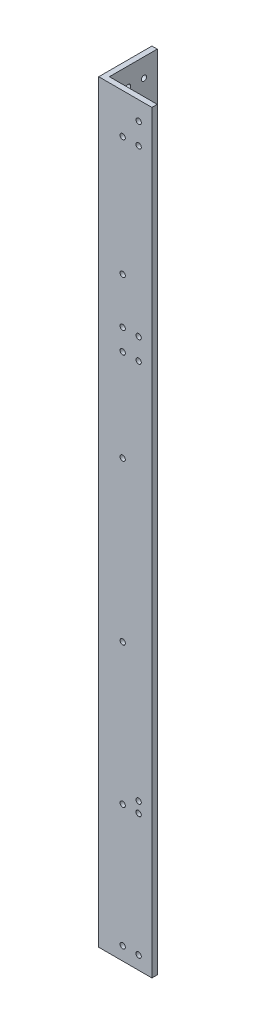
SolidWorks part; units mm, degrees
ref_plane "Front Plane" through (0, 0, 0) normal (0, 0, 1) x (1, 0, 0)
ref_plane "Top Plane" through (0, 0, 0) normal (0, 1, 0) x (1, 0, 0)
ref_plane "Right Plane" through (0, 0, 0) normal (1, 0, 0) x (0, 0, -1)
sketch "Sketch2" plane through (0, 0, 0) normal (0, 1, 0) x (1, 0, 0)
  line L0 (0, 31.75) -> (3.175, 31.75)
  line L1 (3.175, 31.75) -> (3.175, 3.175)
  line L2 (3.175, 3.175) -> (31.75, 3.175)
  line L3 (31.75, 3.175) -> (31.75, 0)
  line L4 (31.75, 0) -> (0, 0)
  line L5 (0, 0) -> (0, 31.75)
  point P9 (1.5875, 31.75)
  point P10 (31.75, 1.5875)
  dimension "D4" = 3.175
  dimension "D1" = 31.75
  dimension "D2" = 31.75
  dimension "D3" = 3.175
extrude "Boss-Extrude1" add sketch "Sketch2" along normal blind 450
sketch "RightSideHoles-Sketch3" plane through (0, 0, 0) normal (0, 0, 1) x (1, 0, 0)
  line L0 (0, 0) -> (31.75, 0) construction
  line L1 (0, 450) -> (31.75, 450) construction
  line L3 (0, 450) -> (0, 0) construction
  circle A0 centre (14.2875, 81.1125) radius 1.5875
  circle A1 centre (23.8125, 81.1125) radius 1.5875
  circle A3 centre (23.8125, 87.4625) radius 1.5875
  circle A5 centre (14.2875, 426.1875) radius 1.5875
  circle A6 centre (23.8125, 438.8875) radius 1.5875
  circle A7 centre (23.8125, 426.1875) radius 1.5875
  circle A8 centre (14.2875, 327.6026) radius 1.5875
  circle A9 centre (23.8125, 327.6026) radius 1.5875
  circle A10 centre (14.2875, 314.9026) radius 1.5875
  circle A11 centre (23.8125, 314.9026) radius 1.5875
  circle A12 centre (14.2875, 7.9375) radius 1.5875
  circle A13 centre (23.8125, 7.9375) radius 1.5875
  circle A14 centre (14.2875, 165) radius 1.5875
  circle A15 centre (14.2875, 260) radius 1.5875
  circle A16 centre (14.2875, 355) radius 1.5875
  dimension "D4" = 3.175
  dimension "D1" = 81.1125
  dimension "D2" = 14.2875
  dimension "D12" = 7.9375
  dimension "D7" = 12.7
  dimension "D3" = 9.525
  dimension "D10" = 327.6026
  dimension "D11" = 165
  dimension "D13" = 95
  dimension "D14" = 95
  dimension "D5" = 6.35
  dimension "D6" = 12.7
  dimension "D8" = 11.1125
sketch "FrontSideHoles-Sketch4" plane through (0, 0, 0) normal (-1, 0, 0) x (0, 0, 1)
  line L0 (-31.75, 450) -> (0, 450) construction
  line L1 (0, 450) -> (0, 0) construction
  line L3 (-31.75, 0) -> (0, 0) construction
  circle A0 centre (-23.8125, 81.1125) radius 1.5875
  circle A2 centre (-23.8125, 87.4625) radius 1.5875
  circle A3 centre (-14.2875, 87.4625) radius 1.5875
  circle A4 centre (-23.8125, 438.8875) radius 1.5875
  circle A5 centre (-14.2875, 438.8875) radius 1.5875
  circle A6 centre (-23.8125, 426.1875) radius 1.5875
  circle A8 centre (-14.2875, 333.1776) radius 2
  circle A9 centre (-14.2875, 314.6526) radius 2
  circle A10 centre (-14.2875, 165) radius 1.5875
  circle A11 centre (-14.2875, 260) radius 1.5875
  circle A12 centre (-14.2875, 355) radius 1.5875
  circle A13 centre (-23.8125, 7.9375) radius 1.5875
  circle A14 centre (-14.2875, 7.9375) radius 1.5875
  dimension "D4" = 3.175
  dimension "D7" = 12.7
  dimension "D13" = 95
  dimension "D14" = 95
  dimension "D5" = 6.35
  dimension "D16" = 4
  dimension "D6" = 11.1125
  dimension "D9" = 18.525
  dimension "D10" = 14.2875
  dimension "D8" = 314.6526
  dimension "D12" = 165
  dimension "D15" = 7.9375
  dimension "D2" = 14.2875
  dimension "D11" = 9.525
  dimension "D3" = 81.1125
extrude "RightSideHoles-Cut-Extrude1" cut sketch "RightSideHoles-Sketch3" against normal blind 3.175
extrude "FrontSideHoles-Cut-Extrude2" cut sketch "FrontSideHoles-Sketch4" against normal blind 3.175
equation "\"RailThickness\"= .125in'Spec"
equation "\"VSWidth\"= 1.25in'Spec"
equation "\"VSHeight\"= 1.25in'Spec"
equation "\"VSLength\"= 450mm"
equation "\"HoleOffsetFromEdge\"= \"RailThickness\" * 2.5"
equation "\"HoleOffsetFromSide\"= \"RailThickness\" * 3.5"
equation "\"LegHeight\"= 70mm'Space needed for PSU/Stepper/Electronics"
equation "\"VSBottomSideRailHoleY1FromBottomOfLowerRail\"= \"V1 BottomOfLowerRail\" + \"HoleOffsetFromSide\"'Equals 70.1125"
equation "\"VSSideRailHoleX1FromSide\"= \"HoleOffsetFromSide\" + \"RailThickness\""
equation "\"FasteningHoleDiameter\"= .125in"
equation "\"VSBottomSideRailHoleY2FromY1\"= \"LowerRailHeight\" - \"HoleOffsetFromSide\" - \"HoleOffsetFromEdge\"'Equals 6.35"
equation "\"VSTopSideRailHoleY1FromEdge\"= \"HoleOffsetFromEdge\" + \"RailThickness\""
equation "\"D4@RightSideHoles-Sketch3\" = \"FasteningHoleDiameter\""
equation "\"D1@RightSideHoles-Sketch3\" = \"VSBottomSideRailHoleY1FromBottomOfLowerRail\""
equation "\"D2@RightSideHoles-Sketch3\" = \"VSSideRailHoleX1FromSide\""
equation "\"D1@Boss-Extrude1\"=\"VSLength\""
equation "\"D4@FrontSideHoles-Sketch4\" = \"FasteningHoleDiameter\""
equation "\"D6@FrontSideHoles-Sketch4\" = \"VSTopSideRailHoleY1FromEdge\""
equation "\"VSMidSideRailHoleY1FromV8TopOfMidSideRail\"= \"V8 ToTopOfMidSideRail\" - \"HoleOffsetFromEdge\"'Equals 308.2875"
equation "\"LowerRailHeight\"= 1.00in"
equation "\"D2@Sketch2\"=\"VSWidth\""
equation "\"D1@Sketch2\"=\"VSHeight\""
equation "\"TopRailHeight\"= 1.25in"
equation "\"MidSideRailHeight\"= 1.25in"
equation "\"D12@RightSideHoles-Sketch3\"=\"HoleOffsetFromEdge\""
equation "\"VSMidSideRailHoleY2FromY1\"= \"MidSideRailHeight\" - \"HoleOffsetFromSide\" - \"HoleOffsetFromEdge\"'Equals 12.7"
equation "\"D7@RightSideHoles-Sketch3\"=\"VSMidSideRailHoleY2FromY1\""
equation "\"VSTopSideRailHoleY2FromY1\"= \"TopRailHeight\" - \"VSTopSideRailHoleY1FromEdge\" - \"HoleOffsetFromEdge\"'Equals 12.7"
equation "\"D7@FrontSideHoles-Sketch4\"=\"VSTopSideRailHoleY2FromY1\""
equation "\"VSSideRailHoleX2FromX1\"= \"VSWidth\" - \"VSSideRailHoleX1FromSide\" - \"HoleOffsetFromEdge\""
equation "\"D3@RightSideHoles-Sketch3\"=\"VSSideRailHoleX2FromX1\""
equation "\"1mmSpacer\"= 1mm"
equation "\"20TGT2PulleyWidth\"= 8.7mm'The STL of the Pulley in the diagram is a bit larger"
equation "\"BeltTensionerUpperLowerWallThickness\"= 7mm"
equation "\"BeltTensionerInnerHeight\"= \"20TGT2PulleyWidth\" * 2 + \"1mmSpacer\" * 3"
equation "\"BeltTensionerHeight\"= \"BeltTensionerInnerHeight\" + \"BeltTensionerUpperLowerWallThickness\" * 2"
equation "\"D9@FrontSideHoles-Sketch4\"=\"VSBeltTensionerHoleY2FromY1\""
equation "\"VSBeltTensionerHoleY1FromBottom\"= \"V9 FromBottomGantryPulleyToBottomOfBeltTensioner\" + \"HoleOffsetFromEdge\""
equation "\"VSBeltTensionerHoleY2FromY1\"= \"BeltTensionerHeight\" - \"HoleOffsetFromEdge\" * 2"
equation "\"V1 BottomOfLowerRail\"= \"LegHeight\""
equation "\"StepperShaftLength\"= 24mm'Pulley will be attached to the end"
equation "\"ZAxisLeadScrewLength\"= 200mm"
equation "\"LM8UUHeight\"= 24mm'Spec"
equation "\"V2 ToBedAtTopOfZAxis\" = \"V1 BottomOfLowerRail\" - \"LowerEnclosureThickness\" + \"StepperShaftLength\" + \"ZAxisLeadScrewLength\" - \"LM8UUHeight\" / 2"
equation "\"HotEndToTopOfXAxisGB\"= 63.315144mm'Measured from the100.Should be 63.315144"
equation "\"TopOfGBToBottomOfLinearRail\"= \"LinearGBWidth\" / 2 + \"LinearRailWidth\" / 2"
equation "\"LinearGBWidth\"= 27mm'Spec"
equation "\"V5 ToBottomOfXAxisLinearRail\"= \"V4 ToTopOfBuildPlate/HotEndTip\" + \"HotEndToTopOfXAxisGB\" - \"TopOfGBToBottomOfLinearRail\""
equation "\"LinearRailWidth\"= 12mm'Spec"
equation "\"V6 ToBottomOfGantryPulley\"= \"V5 ToBottomOfXAxisLinearRail\" - \"DistanceFromGABTopToLowerPulley\""
equation "\"GABUpperHeight\"= 6mm"
equation "\"GABMidWallHeight\"= 28mm'Must equal 28 or changes alignment"
equation "\"GABMidShortRiserHeight\"= \"GABMidWallHeight\" / 2 - \"20TGT2PulleyWidth\"'Equals 5.3"
equation "\"GABRiserBossOffset\"= 0.8mm'Aligns Pulleys"
equation "\"DistanceFromGABTopToLowerPulley\"= \"GABUpperHeight\" + \"GABMidWallHeight\" - \"GABMidShortRiserHeight\" + \"GABRiserBossOffset\" / 2"
equation "\"V7 ToTopOfMidBackRail\"= \"V6 ToBottomOfGantryPulley\" + \"StepperShaftLength\""
equation "\"D10@RightSideHoles-Sketch3\"=\"VSMidSideRailHoleY1FromV8TopOfMidSideRail\""
equation "\"BedToBuildPlateStandoffLength\"= 15mm"
equation "\"BuildPlateHeight\"= 8mm'Spec"
equation "\"V4 ToTopOfBuildPlate/HotEndTip\" = \"V2 ToBedAtTopOfZAxis\" + \"BedToBuildPlateStandoffLength\" + \"BuildPlateHeight\""
equation "\"D8@FrontSideHoles-Sketch4\"=\"VSBeltTensionerHoleY1FromBottom\""
equation "\"V8 ToTopOfMidSideRail\"= \"V7 ToTopOfMidBackRail\" - \"RailThickness\""
equation "\"V9 FromBottomGantryPulleyToBottomOfBeltTensioner\"= \"V6 ToBottomOfGantryPulley\" - \"BeltTensionerUpperLowerWallThickness\" - \"1mmSpacer\""
equation "\"BeltTensionerMountingHoleOffsetFromEdge\"= \"HoleOffsetFromEdge\""
equation "\"VSBeltTensionerXMountingHoleOffsetFromSide\"= \"BeltTensionerMountingHoleOffsetFromEdge\" + \"RailThickness\" * 2"
equation "\"D10@FrontSideHoles-Sketch4\"=\"VSBeltTensionerXMountingHoleOffsetFromSide\""
equation "\"VSEnclosureOffsets\"= ( \"VSLength\" - \"LegHeight\" ) / 4"
equation "\"D11@RightSideHoles-Sketch3\"=\"LegHeight\" + \"VSEnclosureOffsets\""
equation "\"D13@RightSideHoles-Sketch3\"=\"VSEnclosureOffsets\""
equation "\"D14@RightSideHoles-Sketch3\"=\"VSEnclosureOffsets\""
equation "\"D12@FrontSideHoles-Sketch4\"= \"LegHeight\" + \"VSEnclosureOffsets\""
equation "\"D13@FrontSideHoles-Sketch4\"=\"VSEnclosureOffsets\""
equation "\"D14@FrontSideHoles-Sketch4\"=\"VSEnclosureOffsets\""
equation "\"D15@FrontSideHoles-Sketch4\"=\"HoleOffsetFromEdge\""
equation "\"D2@FrontSideHoles-Sketch4\"=\"VSSideRailHoleX1FromSide\""
equation "\"D5@FrontSideHoles-Sketch4\"=\"VSBottomSideRailHoleY2FromY1\""
equation "\"D3@FrontSideHoles-Sketch4\"=\"VSBottomSideRailHoleY1FromBottomOfLowerRail\""
equation "\"D5@RightSideHoles-Sketch3\"=\"VSBottomSideRailHoleY2FromY1\""
equation "\"D6@RightSideHoles-Sketch3\"=\"VSTopSideRailHoleY2FromY1\""
equation "\"D8@RightSideHoles-Sketch3\"=\"VSTopSideRailHoleY1FromEdge\""
equation "\"BeltTensionerMountingHoleDiameter\"= 4.0mm"
equation "\"D16@FrontSideHoles-Sketch4\"=\"BeltTensionerMountingHoleDiameter\""
equation "\"LowerEnclosureThickness\"= 5mm"
